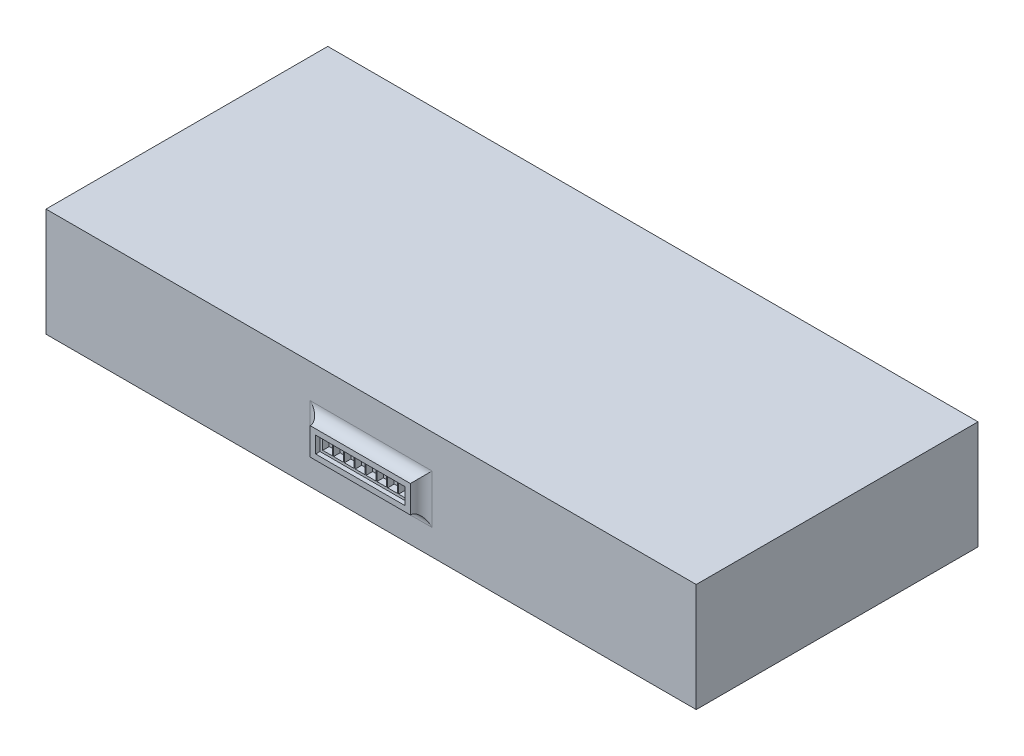
SolidWorks part; units mm, degrees
ref_plane "Front Plane" through (0, 0, 0) normal (0, 0, 1) x (1, 0, 0)
ref_plane "Top Plane" through (0, 0, 0) normal (0, 1, 0) x (1, 0, 0)
ref_plane "Right Plane" through (0, 0, 0) normal (1, 0, 0) x (0, 0, -1)
sketch "Sketch1" plane through (0, 0, 0) normal (0, 1, 0) x (1, 0, 0)
  line L1 (-300, 130) -> (300, 130)
  line L2 (-300, 130) -> (-300, -130)
  line L3 (-300, -130) -> (300, -130)
  line L4 (300, 130) -> (300, -130)
  line L5 (-300, 130) -> (300, -130) construction
  line L6 (-300, -130) -> (300, 130) construction
  point P0 (0, 0)
  dimension "D1" = 260
  dimension "D2" = 600
extrude "Boss-Extrude1" add sketch "Sketch1" along normal blind 100
shell "Shell1" thickness 2
sketch "Sketch2" plane through (0, 0, 130) normal (0, 0, 1) x (1, 0, 0)
  line L0 (-41.2203, 53.8039) -> (-41.2203, 38.6499)
  line L1 (-46.2203, 58.8039) -> (46.2203, 58.8039)
  line L2 (-46.2203, 58.8039) -> (-46.2203, 33.6499)
  line L3 (-46.2203, 33.6499) -> (46.2203, 33.6499)
  line L4 (46.2203, 58.8039) -> (46.2203, 33.6499)
  line L5 (-46.2203, 58.8039) -> (46.2203, 33.6499) construction
  line L6 (-46.2203, 33.6499) -> (46.2203, 58.8039) construction
  line L7 (-41.2203, 38.6499) -> (41.2203, 38.6499)
  line L8 (41.2203, 53.8039) -> (41.2203, 38.6499)
  line L9 (-41.2203, 53.8039) -> (41.2203, 53.8039)
  line L10 (-28.6556, 51.5506) -> (-19.6404, 40.9032) construction
  line L11 (-38.6556, 51.5506) -> (-29.6404, 51.5506)
  line L12 (-38.6556, 51.5506) -> (-38.6556, 40.9032)
  line L13 (-38.6556, 40.9032) -> (-29.6404, 40.9032)
  line L14 (-29.6404, 51.5506) -> (-29.6404, 40.9032)
  line L15 (-38.6556, 51.5506) -> (-29.6404, 40.9032) construction
  line L16 (-38.6556, 40.9032) -> (-29.6404, 51.5506) construction
  line L17 (-28.6556, 40.9032) -> (-19.6404, 51.5506) construction
  line L18 (-28.6556, 51.5506) -> (-28.6556, 40.9032)
  line L19 (-28.6556, 51.5506) -> (-19.6404, 51.5506)
  line L20 (-19.6404, 51.5506) -> (-19.6404, 40.9032)
  line L21 (-28.6556, 40.9032) -> (-19.6404, 40.9032)
  line L22 (-18.6556, 51.5506) -> (-9.6404, 40.9032) construction
  line L23 (-18.6556, 40.9032) -> (-9.6404, 51.5506) construction
  line L24 (-18.6556, 51.5506) -> (-18.6556, 40.9032)
  line L25 (-18.6556, 51.5506) -> (-9.6404, 51.5506)
  line L26 (-9.6404, 51.5506) -> (-9.6404, 40.9032)
  line L27 (-18.6556, 40.9032) -> (-9.6404, 40.9032)
  line L28 (-8.6556, 51.5506) -> (0.3596, 40.9032) construction
  line L29 (-8.6556, 40.9032) -> (0.3596, 51.5506) construction
  line L30 (-8.6556, 51.5506) -> (-8.6556, 40.9032)
  line L31 (-8.6556, 51.5506) -> (0.3596, 51.5506)
  line L32 (0.3596, 51.5506) -> (0.3596, 40.9032)
  line L33 (-8.6556, 40.9032) -> (0.3596, 40.9032)
  line L34 (1.3444, 51.5506) -> (10.3596, 40.9032) construction
  line L35 (1.3444, 40.9032) -> (10.3596, 51.5506) construction
  line L36 (1.3444, 51.5506) -> (1.3444, 40.9032)
  line L37 (1.3444, 51.5506) -> (10.3596, 51.5506)
  line L38 (10.3596, 51.5506) -> (10.3596, 40.9032)
  line L39 (1.3444, 40.9032) -> (10.3596, 40.9032)
  line L40 (11.3444, 51.5506) -> (20.3596, 40.9032) construction
  line L41 (11.3444, 40.9032) -> (20.3596, 51.5506) construction
  line L42 (11.3444, 51.5506) -> (11.3444, 40.9032)
  line L43 (11.3444, 51.5506) -> (20.3596, 51.5506)
  line L44 (20.3596, 51.5506) -> (20.3596, 40.9032)
  line L45 (11.3444, 40.9032) -> (20.3596, 40.9032)
  line L46 (21.3444, 51.5506) -> (30.3596, 40.9032) construction
  line L47 (21.3444, 40.9032) -> (30.3596, 51.5506) construction
  line L48 (21.3444, 51.5506) -> (21.3444, 40.9032)
  line L49 (21.3444, 51.5506) -> (30.3596, 51.5506)
  line L50 (30.3596, 51.5506) -> (30.3596, 40.9032)
  line L51 (21.3444, 40.9032) -> (30.3596, 40.9032)
  line L52 (31.3444, 51.5506) -> (40.3596, 40.9032) construction
  line L53 (31.3444, 40.9032) -> (40.3596, 51.5506) construction
  line L54 (31.3444, 51.5506) -> (31.3444, 40.9032)
  line L55 (31.3444, 51.5506) -> (40.3596, 51.5506)
  line L56 (40.3596, 51.5506) -> (40.3596, 40.9032)
  line L57 (31.3444, 40.9032) -> (40.3596, 40.9032)
  point P0 (0, 46.2269)
  point P9 (-34.148, 46.2269)
  point P15 (-24.148, 46.2269)
  point P20 (-14.148, 46.2269)
  point P25 (-4.148, 46.2269)
  point P30 (5.852, 46.2269)
  point P35 (15.852, 46.2269)
  point P40 (25.852, 46.2269)
  point P45 (35.852, 46.2269)
  dimension "D1" = 5
  dimension "D2" = 8
extrude "Boss-Extrude2" add sketch "Sketch2" along normal blind 10 contours L4 L1 L2 L3 L0 L9 L8 L7 region at (0, 57.8459, 130)
extrude "Boss-Extrude3" add sketch "Sketch2<3>" along normal blind 6 contours L9 L0 L7 L8 L57 L54 L55 L56 L51 L48 L49 L50 L45 L42 L43 L44 L39 L36 L37 L38 L33 L30 L31 L32 L27 L24 L25 L26 L21 L18 L19 L20 L11 L14 L13 L12 region at (0, 52.9657, 130)
sketch "Sketch2<3>" plane through (0, 0, 130) normal (0, 0, 1) x (1, 0, 0) same geometry as "Sketch2"
fillet "Fillet1" radius 10 4 edges at (46.2203, 46.2269, 130) (0, 58.8039, 130) (-46.2203, 46.2269, 130) (0, 33.6499, 130)
